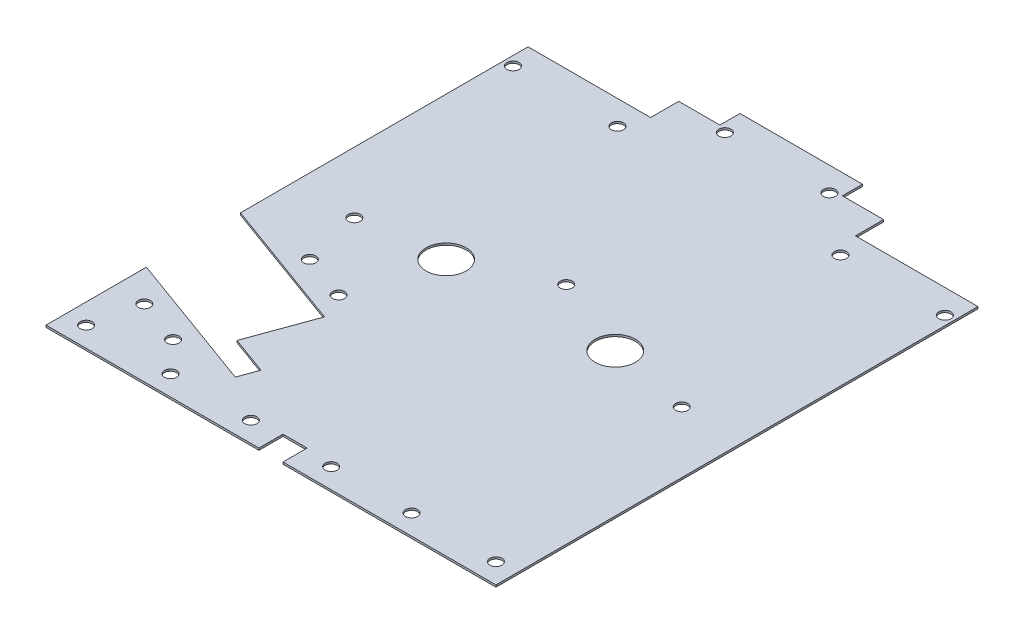
SolidWorks part; units mm, degrees
ref_plane "Front Plane" through (0, 0, 0) normal (0, 0, 1) x (1, 0, 0)
ref_plane "Top Plane" through (0, 0, 0) normal (0, 1, 0) x (1, 0, 0)
ref_plane "Right Plane" through (0, 0, 0) normal (1, 0, 0) x (0, 0, -1)
sketch "Croquis1" plane through (0, 0, 0) normal (0, 1, 0) x (1, 0, 0)
  line L0 (0, 83.2697) -> (0, -74.6341) construction
  line L1 (56, 66) -> (-56, 66)
  line L2 (56, 66) -> (56, -66)
  line L3 (56, -66) -> (-56, -66)
  line L4 (-56, 66) -> (-56, -66)
  line L5 (56, 66) -> (-56, -66) construction
  line L6 (56, -66) -> (-56, 66) construction
  point P0 (0, 0)
  dimension "D1" = 132
  dimension "D2" = 112
sheet metal parameters "Chapa metálica1" thickness 0.5 parameters "D1"=0.5
base flange "Brida base1" sketch "Croquis1" thickness 0.5 reverse thickness direction no parameters "D1"=0.5
sketch "Croquis5" plane through (0, 0, 0) normal (0, 1, 0) x (1, 0, 0)
  line L0 (0, 66) -> (-15.25, 66)
  line L1 (56, 66) -> (-56, 66) construction
  line L2 (56, 66) -> (-56, 66) construction
  line L3 (-15.25, 66) -> (-15.25, 61)
  line L4 (-15.25, 61) -> (-25.5, 61)
  line L5 (-25.5, 61) -> (-25.5, 54)
  line L6 (-25.5, 54) -> (-56, 54)
  line L7 (-56, 66) -> (-56, -66) construction
  line L8 (0, -84.2848) -> (0, 85.6944) construction
  line L9 (15.25, 66) -> (15.25, 61)
  line L10 (25.5, 61) -> (25.5, 54)
  line L11 (15.25, 61) -> (25.5, 61)
  line L12 (25.5, 54) -> (56, 54)
  line L13 (15.25, 66) -> (0, 66)
  line L14 (-56, 54) -> (-56, 66)
  line L15 (-56, 66) -> (-15.25, 66)
  line L16 (15.25, 66) -> (56, 66)
  line L17 (56, 66) -> (56, 54)
  line M1 (-56, 66) -> (-56, -66)
  line M3 (56, -66) -> (56, 66)
  line M4 (56, 66) -> (-56, 66)
  dimension "D1" = 30.5
  dimension "D2" = 30.5
  dimension "D3" = 5
  dimension "D4" = 7
extrude "Cortar-Extruir4" cut sketch "Croquis5" against normal blind 10 contours L6 L5 L4 L3 M4 M1 | L10 L12 L9 L11 M3 M4 normal cut yes
sketch "Croquis7" plane through (0, 0, 0) normal (0, 1, 0) x (1, 0, 0)
  line L0 (-40.75, 67.6667) -> (-40.75, -84.4035) construction
  line L1 (0, 81.0819) -> (0, -70.4123) construction
  line L2 (-25.5, 54) -> (-56, 54) construction
  line L3 (15.25, 66) -> (-15.25, 66) construction
  line L4 (-56, 54) -> (-56, -66) construction
  circle A0 centre (-40.75, -4.5) radius 1.5
  circle A1 centre (40.75, -4.5) radius 1.5
  circle A2 centre (0, 7.5) radius 1.5
  dimension "D1" = 3
  dimension "D4" = 3
  dimension "D2" = 58.5
  dimension "D3" = 58.5
  dimension "D5" = 15.25
extrude "Cortar-Extruir5" cut sketch "Croquis7" against normal blind 10 normal cut yes
sketch "Croquis8" plane through (0, 0, 0) normal (0, 1, 0) x (1, 0, 0)
  line L0 (-56, -66) -> (56, -66) construction
  line L1 (-56, 54) -> (-56, -66) construction
  line L2 (-56, -17.5881) -> (-56, -41)
  line L3 (-28.9251, -45.5336) -> (-23.1108, -29.5588)
  line L4 (-28.9251, -45.5336) -> (-19.5282, -48.9538)
  line L6 (-21.2383, -53.6522) -> (-86.6153, -29.857) construction
  line L7 (-23.1108, -29.5588) -> (-56, -17.5881)
  line L8 (-19.5282, -48.9538) -> (-21.2383, -53.6522)
  line L9 (-21.2383, -53.6522) -> (-56, -41)
  line L12 (-13.7138, -32.979) -> (-79.0908, -9.1837) construction
  dimension "D1" = 25
  dimension "D2" = 35
  dimension "D3" = 70
  dimension "D4" = 5
  dimension "D6" = 10
  dimension "D5" = 22
extrude "Cortar-Extruir6" cut sketch "Croquis8" against normal blind 10 normal cut yes
sketch "Croquis9" plane through (0, 0, 0) normal (0, 1, 0) x (1, 0, 0)
  line L0 (0, 72.8963) -> (0, -76.8732) construction
  line L1 (-15.25, 66) -> (-15.25, 61) construction
  line L2 (15.25, 66) -> (-15.25, 66) construction
  line L3 (-40.75, 65.5314) -> (-40.75, 33.209) construction
  line L4 (-25.5, 54) -> (-56, 54) construction
  line L5 (-56, 54) -> (-56, -17.5881) construction
  circle A0 centre (-13, 60) radius 1.5
  circle A1 centre (13, 60) radius 1.5
  circle A2 centre (-53.75, 48) radius 1.5
  circle A3 centre (-27.75, 48) radius 1.5
  circle A4 centre (27.75, 48) radius 1.5
  circle A5 centre (53.75, 48) radius 1.5
  dimension "D1" = 3
  dimension "D4" = 3
  dimension "D2" = 2.25
  dimension "D3" = 6
  dimension "D5" = 6
  dimension "D6" = 2.25
extrude "Cortar-Extruir7" cut sketch "Croquis9" against normal blind 12 normal cut yes
sketch "Croquis10" plane through (0, 0, 0) normal (0, 1, 0) x (1, 0, 0)
  line L0 (-45.8784, -15.9511) -> (-15.4538, -27.0248) construction
  line L1 (-80.8008, -20.2673) -> (-6.8449, -47.185) construction
  line L2 (-50.9812, -73.9811) -> (-28.5511, -12.355) construction
  line L3 (-51.5614, -47.9364) -> (-25.0459, -57.5873) construction
  line L4 (-56, -17.5881) -> (-23.1108, -29.5588) construction
  line L5 (-21.2383, -53.6522) -> (-56, -41) construction
  circle A0 centre (-37.3464, -18.9771) radius 1.5
  circle A1 centre (-26.0701, -23.0813) radius 1.5
  circle A2 centre (-37.0659, -53.2918) radius 1.5
  circle A3 centre (-48.3422, -49.1876) radius 1.5
  dimension "D3" = 3
  dimension "D1" = 5
  dimension "D2" = 5
  dimension "D4" = 12
  dimension "D5" = 11
extrude "Cortar-Extruir8" cut sketch "Croquis10" against normal blind 10 normal cut yes
sketch "Croquis11" plane through (0, 0, 0) normal (0, 1, 0) x (1, 0, 0)
  line L0 (-62.6561, -61) -> (63.4654, -61) construction
  line L1 (0, 94.275) -> (0, -98.6411) construction
  line L2 (-56, -66) -> (56, -66) construction
  line L3 (-56, -41) -> (-56, -66) construction
  circle A0 centre (-10, -61) radius 1.5
  circle A1 centre (-30, -61) radius 1.5
  circle A2 centre (30, -61) radius 1.5
  circle A3 centre (10, -61) radius 1.5
  circle A4 centre (-51, -61) radius 1.5
  circle A5 centre (51, -61) radius 1.5
  dimension "D2" = 3
  dimension "D3" = 3
  dimension "D6" = 3
  dimension "D1" = 5
  dimension "D4" = 10
  dimension "D5" = 20
  dimension "D7" = 5
extrude "Cortar-Extruir9" cut sketch "Croquis11" against normal blind 10 normal cut yes
sketch "Croquis12" plane through (0, 0, 0) normal (0, 1, 0) x (1, 0, 0)
  line L1 (-3, -66) -> (-3, -60)
  line L2 (-56, -66) -> (56, -66) construction
  line L3 (-3, -60) -> (3, -60)
  line L4 (-3, -66) -> (3, -66)
  line L5 (0, 84.2043) -> (0, -80.1585) construction
  line L6 (3, -66) -> (3, -60)
  point P10 (0, -66)
  point P11 (0, -60)
  dimension "D1" = 6
  dimension "D2" = 6
extrude "Cortar-Extruir10" cut sketch "Croquis12" against normal blind 10 normal cut yes
flat pattern "Chapa desplegada1"
sketch "Líneas de pliegue1" plane through (0, 0, 0) normal (0, 1, 0) x (-1, 0, 0)
sketch3d "Cuadro delimitador1"
  line L0 (0, 0, 0) -> (0, -132, 0) construction
  line L1 (112, 0, 0) -> (112, -132, 0) construction
  line L2 (0, 0, 0) -> (112, 0, 0) construction
  line L3 (0, -132, 0) -> (112, -132, 0) construction
sketch "Croquis13" plane through (0, 0, 0) normal (0, 1, 0) x (1, 0, 0)
  line L0 (-20.375, 71.7416) -> (-20.375, -75.7645) construction
  line L1 (20.375, 71.7416) -> (20.375, -73.0826) construction
  line L2 (-62.489, -2.0114) -> (61.9526, -2.0114) construction
  circle A0 centre (-20.375, -2.0114) radius 5
  circle A1 centre (20.375, -0.6705) radius 5
  dimension "D1" = 10
extrude "Cortar-Extruir11" cut sketch "Croquis13" against normal blind 10 normal cut yes
